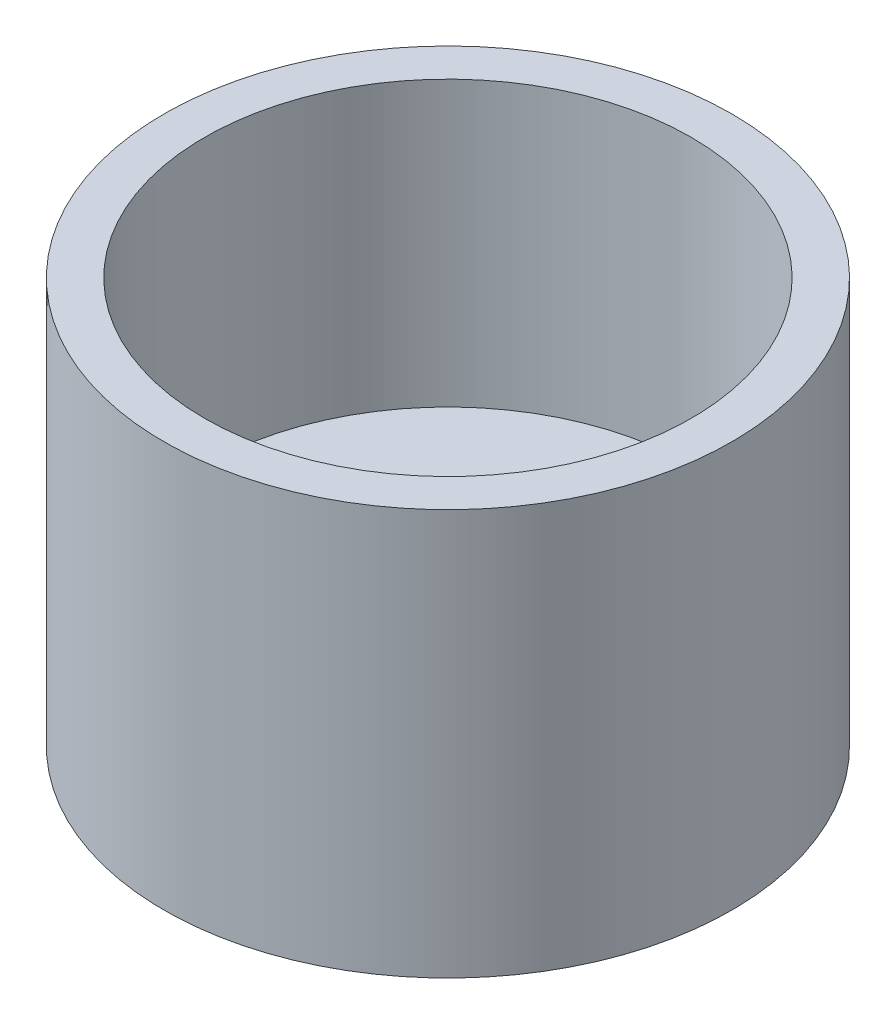
SolidWorks part; units mm, degrees
material "1.0035 (S185)"
ref_plane "Piano frontale" through (0, 0, 0) normal (0, 0, 1) x (1, 0, 0)
ref_plane "Piano superiore" through (0, 0, 0) normal (0, 1, 0) x (1, 0, 0)
ref_plane "Piano destro" through (0, 0, 0) normal (1, 0, 0) x (0, 0, -1)
sketch "Schizzo1" plane through (0, 0, 0) normal (0, 0, 1) x (1, 0, 0)
  line L0 (0, 0) -> (-14, 0)
  line L1 (-14, 0) -> (-14, 20)
  line L2 (-14, 20) -> (-12, 20)
  line L3 (-12, 20) -> (-12, 6)
  line L4 (-12, 6) -> (0, 6)
  line L5 (0, 6) -> (0, 0)
  line L6 (0, 0) -> (0, 10.8439) construction
  dimension "D1" = 28
  dimension "D2" = 24
  dimension "D3" = 6
  dimension "D4" = 20
revolve "Rivoluzione1" add sketch "Schizzo1" angle 360 about L6
sketch "Schizzo2" plane through (0, 0, 0) normal (0, -1, 0) x (1, 0, 0)
  circle A0 centre (0, 0) radius 1
  dimension "D1" = 2
extrude "Taglio-Estrusione1" cut sketch "Schizzo2" against normal blind 10
sketch "Schizzo3" plane through (0, 0, 0) normal (0, -1, 0) x (1, 0, 0)
  circle A0 centre (0, 0) radius 1.019
  circle A1 centre (0, 0) radius 1.5875
  dimension "D1" = 3.175
extrude "Estrusione-Estrusione1" [suppressed] add sketch "Schizzo3" along normal blind 8
sketch "Schizzo4" plane through (0, 0, 0) normal (0, 0, 1) x (1, 0, 0)
  line L0 (0, 0) -> (0, -9.8437)
